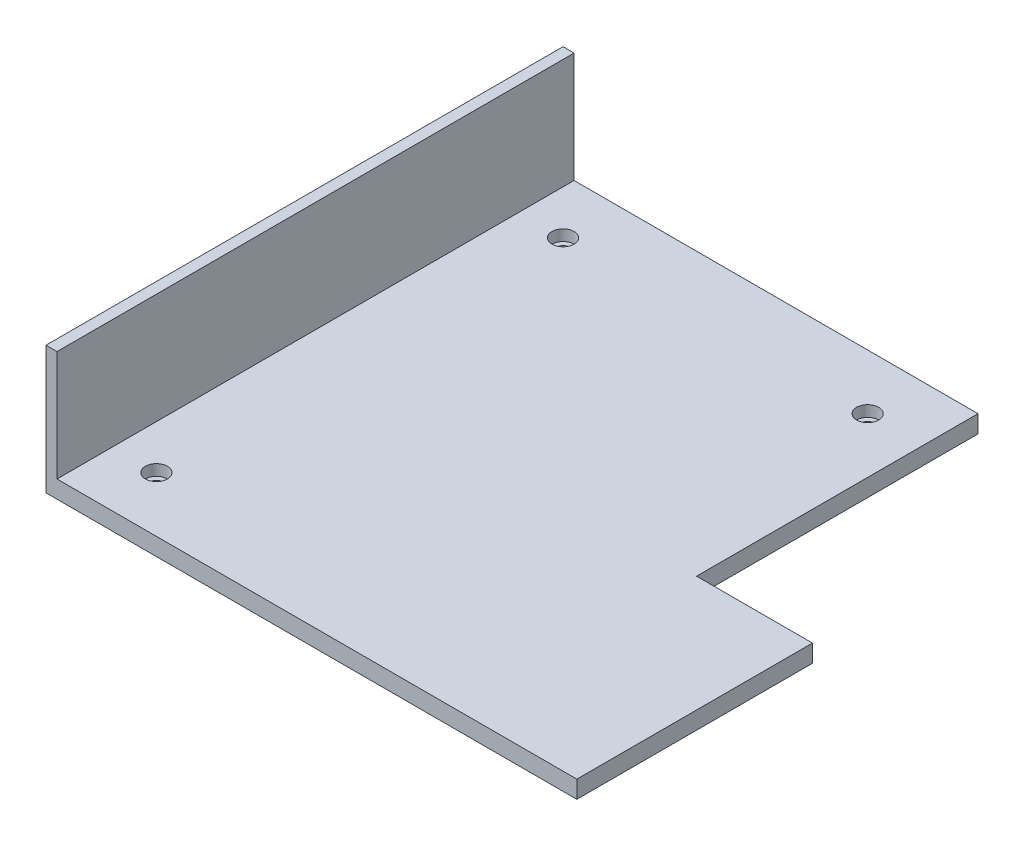
SolidWorks part; units mm, degrees
ref_plane "Front Plane" through (0, 0, 0) normal (0, 0, 1) x (1, 0, 0)
ref_plane "Top Plane" through (0, 0, 0) normal (0, 1, 0) x (1, 0, 0)
ref_plane "Right Plane" through (0, 0, 0) normal (1, 0, 0) x (0, 0, -1)
sketch "Sketch1" plane through (0, 0, 0) normal (0, 1, 0) x (1, 0, 0)
  line L1 (-96.2, 93.7) -> (96.2, 93.7)
  line L2 (-96.2, 93.7) -> (-96.2, -93.7)
  line L3 (-96.2, -93.7) -> (96.2, -93.7)
  line L4 (96.2, 93.7) -> (96.2, -93.7)
  line L5 (-96.2, 93.7) -> (96.2, -93.7) construction
  line L6 (-96.2, -93.7) -> (96.2, 93.7) construction
  point P0 (0, 0)
  dimension "D1" = 187.4
  dimension "D2" = 192.4
extrude "Boss-Extrude1" add sketch "Sketch1" along normal blind 6.35
sketch "Sketch2" plane through (0, 6.35, 0) normal (0, 1, 0) x (1, 0, 0)
  line L2 (-92.2, 89.7) -> (-92.2, -89.7)
  line L4 (96.2, -93.7) -> (96.2, 93.7)
  line L5 (96.2, 93.7) -> (-96.2, 93.7)
  line L6 (-96.2, 93.7) -> (-96.2, -93.7)
  line L7 (-96.2, -93.7) -> (96.2, -93.7)
  line L10 (-96.2, 93.7) -> (-96.2, -93.7)
  line L12 (92.2, 89.7) -> (-92.2, 89.7) construction
  line L13 (96.2, 93.7) -> (-96.2, 93.7) construction
  line L14 (92.2, -89.7) -> (92.2, 89.7) construction
  line L15 (96.2, -93.7) -> (96.2, 93.7) construction
  line L16 (-92.2, 89.7) -> (-92.2, 93.7)
  line L17 (96.2, 93.7) -> (-96.2, 93.7) construction
  line L18 (-92.2, 93.7) -> (-96.2, 93.7)
  line L22 (-92.2, -89.7) -> (92.2, -89.7) construction
  line L23 (-96.2, -93.7) -> (96.2, -93.7) construction
  line L24 (-92.2, -89.7) -> (-92.2, -93.7)
  line L25 (-96.2, -93.7) -> (96.2, -93.7) construction
  line L26 (-92.2, -93.7) -> (-96.2, -93.7)
  dimension "D1" = 0
  dimension "D2" = 4
extrude "Boss-Extrude2" add sketch "Sketch2" along normal blind 40
sketch "Sketch4" plane through (0, 6.35, 0) normal (0, 1, 0) x (1, 0, 0)
  line L0 (-92.2, -93.7) -> (96.2, -93.7) construction
  line L1 (96.2, 93.7) -> (54.2, 93.7)
  line L2 (96.2, 93.7) -> (96.2, -8.3)
  line L3 (96.2, -8.3) -> (54.2, -8.3)
  line L4 (54.2, 93.7) -> (54.2, -8.3)
  line L5 (-96.2, 93.7) -> (-96.2, -93.7) construction
  dimension "D1" = 85.4
  dimension "D2" = 150.4
extrude "Cut-Extrude1" cut sketch "Sketch4" against normal up to next
sketch "Sketch5" plane through (0, 6.35, 0) normal (0, 1, 0) x (1, 0, 0)
  line L0 (-96.2, 93.7) -> (-96.2, -93.7) construction
  line L1 (54.2, 93.7) -> (-96.2, 93.7) construction
  line L2 (54.2, 93.7) -> (54.2, 53.7) construction
  line L3 (54.2, 53.7) -> (-96.2, 53.7) construction
  line L4 (-96.2, 93.7) -> (-96.2, 53.7) construction
  line L5 (-92.2, -93.7) -> (96.2, -93.7) construction
  line L6 (-96.2, 93.7) -> (-56.2, 93.7) construction
  line L7 (-96.2, 93.7) -> (-96.2, -93.7) construction
  line L8 (-96.2, -93.7) -> (-56.2, -93.7) construction
  line L9 (-56.2, 93.7) -> (-56.2, -93.7) construction
  line L10 (-76.2, -93.7) -> (-76.2, 93.7) construction
  line L11 (54.2, 73.7) -> (-96.2, 73.7) construction
  point P18 (-76.2, 73.7)
  point P20 (-76.2, -73.7)
  point P24 (34.2, 73.7)
  dimension "D1" = 40
  dimension "D2" = 40
  dimension "D3" = 20
  dimension "D4" = 20
hole_wizard "CBORE for M4 SHCS1" positions "Sketch5" profile "Sketch6" counterbore size "M4" standard "ANSI Metric" end condition up to next
sketch "Sketch6" plane through (34.2, 6.35, -73.7) normal (1, 0, 0) x (0, 0, 1)
  line L0 (0, 0) -> (0, 6.35)
  line L1 (0, 6.35) -> (2.25, 6.35)
  line L3 (2.25, 6.35) -> (2.25, 4)
  line L4 (2.25, 4) -> (4, 4)
  line L5 (4, 4) -> (4, 0)
  line L7 (4, 0) -> (0, 0)
  line L11 (0, -6.35) -> (0, 107.95) construction
  dimension "Thru Hole Dia." = 4.5
  dimension "Thru Hole Depth" = 6.35
  dimension "C'Bore Dia." = 8
  dimension "C'Bore Depth" = 4
mirror "Mirror1" [suppressed] of bodies 105
delete or keep bodies "Body-Delete/Keep 1" [suppressed] type delete bodies bodies 105
equation "\"D2@Sketch1\"=384.8/2"
equation "\"D2@Sketch4\"=152.4-2"
equation "\"D1@Sketch4\"=87.4-2"
